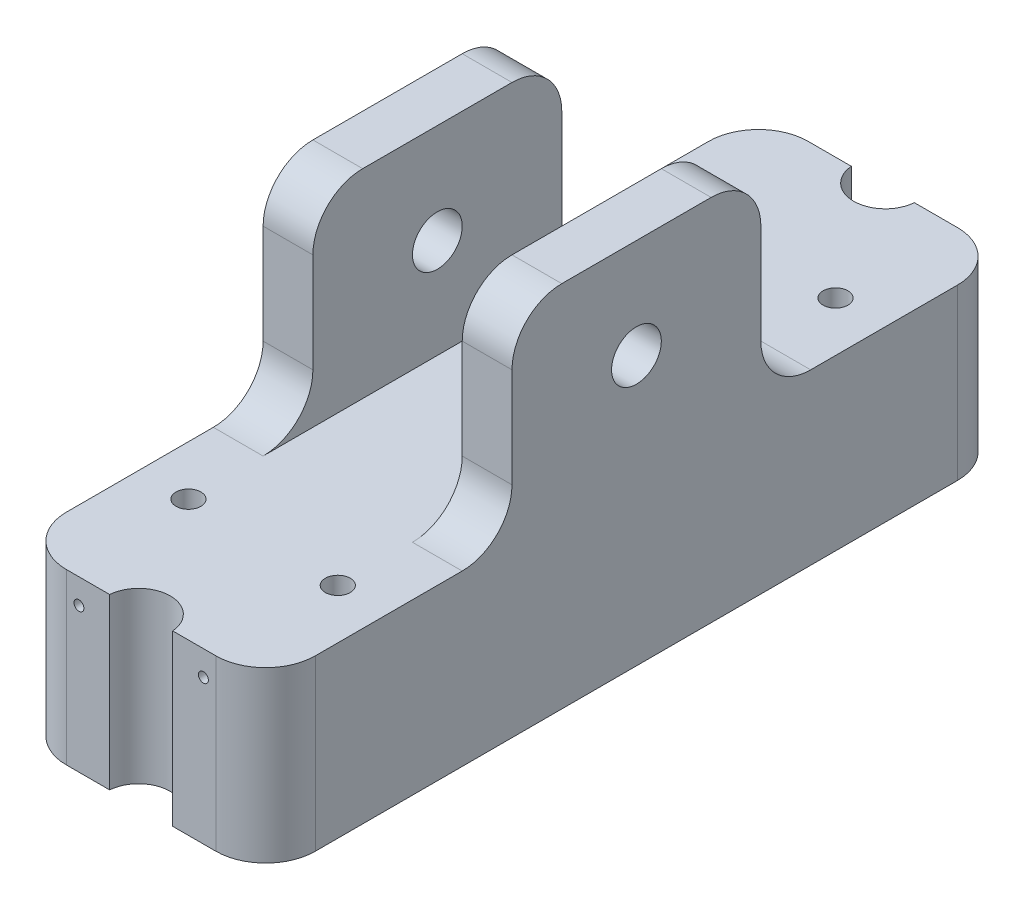
SolidWorks part; units mm, degrees
material "Nylon 101"
ref_plane "Front" through (0, 0, 0) normal (0, 0, 1) x (1, 0, 0)
ref_plane "Top" through (0, 0, 0) normal (0, 1, 0) x (1, 0, 0)
ref_plane "Right" through (0, 0, 0) normal (1, 0, 0) x (0, 0, -1)
sketch "Sketch1" plane through (0, 0, 0) normal (0, 1, 0) x (1, 0, 0)
  line L0 (-25, -75) -> (25, -75) construction
  line L1 (-15, 50) -> (15, 50) construction
  line L2 (0, -75) -> (0, 75) construction
  line L3 (-25, -75) -> (-25, 75)
  line L4 (25, -75) -> (25, 75)
  line L5 (25, 0) -> (0, 0) construction
  line L6 (25, 17) -> (97.2, 17)
  line L7 (25, 17) -> (25, -17)
  line L8 (25, -17) -> (97.2, -17)
  line L9 (97.2, 17) -> (97.2, -17)
  line L10 (-15, 50) -> (-15, -50) construction
  line L11 (-15, -50) -> (15, -50) construction
  line L12 (15, 50) -> (15, -50) construction
  line L13 (-25, -75.5) -> (25, -75.5)
  line L14 (-25, -74.5) -> (25, -74.5)
  line L15 (-25, 75.5) -> (25, 75.5)
  line L16 (-25, 74.5) -> (25, 74.5)
  circle A0 centre (0, 75) radius 6.35
  circle A1 centre (0, -75) radius 6.35
  arc A2 (-25, -75) -> (25, -75) centre (0, -75) ccw
  arc A3 (25, 75) -> (-25, 75) centre (0, 75) ccw
  circle A6 centre (-15, 50) radius 2.5
  circle A7 centre (-15, -50) radius 2.5
  circle A8 centre (15, -50) radius 2.5
  circle A9 centre (15, 50) radius 2.5
  point P8 (0, 0)
  point P24 (0, -50)
  dimension "D2" = 12.7
  dimension "D5" = 25
  dimension "D1" = 5
  dimension "D3" = 150
  dimension "D4" = 25
  dimension "D6" = 25
  dimension "D7" = 34
  dimension "D8" = 72.2
  dimension "D9" = 30
  dimension "D10" = 0.5
  dimension "D11" = 0.5
extrude "Boss-Extrude1" add sketch "Sketch1" along normal blind 10 and the other way blind 24.004 contours A1 L14 L4 L16 A0 L3 A9 A8 A7 A6 region at (0, 0, 0)
sketch "Sketch2" plane through (0, 0, 0) normal (0, 1, 0) x (1, 0, 0)
  line L0 (25, -75) -> (25, 75) construction
  line L1 (25, 25) -> (15, 25)
  line L2 (25, 25) -> (25, -25)
  line L3 (25, -25) -> (15, -25)
  line L4 (15, 25) -> (15, -25)
  line L6 (25, 0) -> (0, 0) construction
  line L7 (25, 0) -> (0, 0) construction
  line L8 (-25, -74.5) -> (-25, 74.5) construction
  line L9 (-25, 25) -> (-15, 25)
  line L10 (-25, 25) -> (-25, -25)
  line L11 (-25, -25) -> (-15, -25)
  line L12 (-15, 25) -> (-15, -25)
  line L13 (0, 0) -> (0, 4.5574) construction
  dimension "D1" = 50
  dimension "D2" = 10
extrude "Boss-Extrude2" add sketch "Sketch2" along normal blind 50
sketch "Sketch4" plane through (25, 0, 0) normal (1, 0, 0) x (0, 0, -1)
  line L0 (-25, 10) -> (25, 10) construction
  line L1 (-74.5, 10) -> (-25, 10) construction
  line L2 (-25, 50) -> (-25, 10) construction
  line L3 (0, 10) -> (0, 50) construction
  line L4 (-25, 50) -> (25, 50) construction
  circle A0 centre (0, 30) radius 5
  dimension "D1" = 10
extrude "Cut-Extrude2" cut sketch "Sketch4" against normal through all
fillet "Fillet1" radius 10 12 edges at (-20, 50, -25) (-20, 50, 25) (-20, 10, 25) (-20, 10, -25) (20, 50, -25) (20, 50, 25) (20, 10, 25) (20, 10, -25) (25, -7.002, -74.5) (-25, -7.002, -74.5) (-25, -7.002, 74.5) (25, -7.002, 74.5)
sketch "Sketch5" plane through (0, 0, 74.5) normal (0, 0, 1) x (1, 0, 0)
  line L0 (-12.5, 0) -> (-12.5, 10) construction
  line L1 (12.5, 10) -> (12.5, 0) construction
  line L2 (-15, 10) -> (-6.3303, 10) construction
  line L3 (6.3303, 10) -> (15, 10) construction
  line L4 (0, 0) -> (0, 2.4841) construction
  circle A0 centre (-12.5, 5) radius 1
  circle A1 centre (12.5, 5) radius 1
  dimension "D1" = 2
  dimension "D2" = 12.5
extrude "Cut-Extrude3" cut sketch "Sketch5" against normal blind 5
extrude "Cut-Extrude4" cut sketch "Sketch5<2>" along normal blind 5 from surface starting at face at (10.6651, -7.002, -74.5)
sketch "Sketch5<2>" plane through (0, 0, 74.5) normal (0, 0, 1) x (1, 0, 0) same geometry as "Sketch5"
